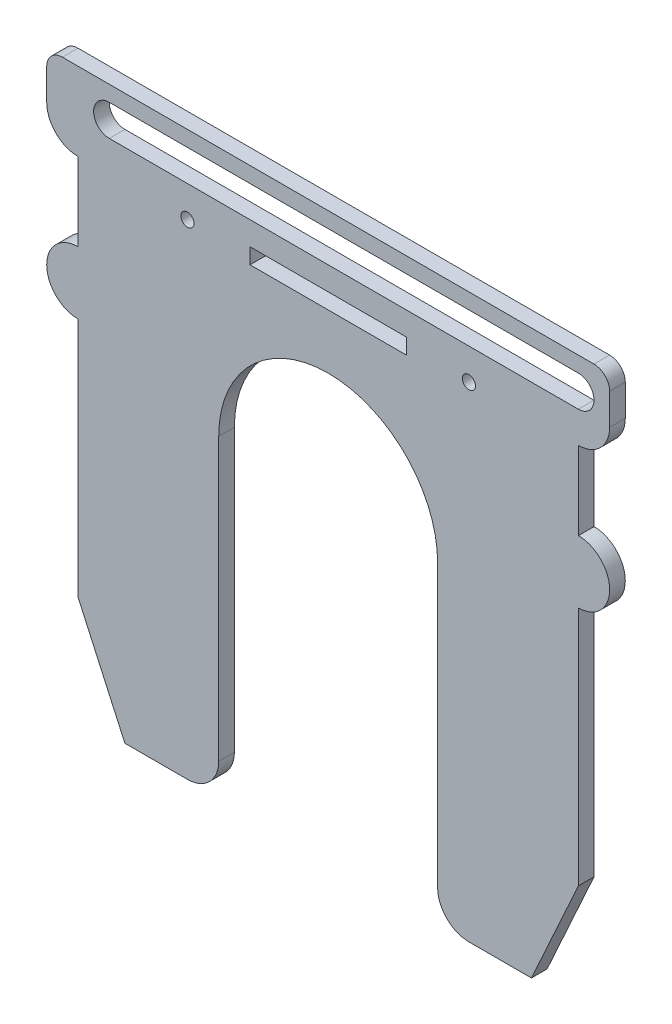
SolidWorks part; units mm, degrees
ref_plane "Front Plane" through (0, 0, 0) normal (0, 0, 1) x (1, 0, 0)
ref_plane "Top Plane" through (0, 0, 0) normal (0, 1, 0) x (1, 0, 0)
ref_plane "Right Plane" through (0, 0, 0) normal (1, 0, 0) x (0, 0, -1)
sketch "Sketch1" plane through (0, 0, 0) normal (0, 0, 1) x (1, 0, 0)
  line L0 (-160, 170) -> (-10, 170) construction
  line L1 (-10, 0) -> (-45, 0)
  line L2 (0, 10) -> (0, 175)
  line L3 (-5, 180) -> (-175, 180)
  line L4 (-180, 10) -> (-180, 175)
  line L5 (-160, 175) -> (-10, 175)
  line L6 (-160, 165) -> (-10, 165)
  line L7 (-125, 10) -> (-125, 100)
  line L8 (-55, 10) -> (-55, 100)
  line L9 (-135, 0) -> (-170, 0)
  arc A0 (-160, 175) -> (-160, 165) centre (-160, 170) ccw
  arc A1 (-10, 165) -> (-10, 175) centre (-10, 170) ccw
  arc A2 (0, 175) -> (-5, 180) centre (-5, 175) ccw
  arc A3 (-175, 180) -> (-180, 175) centre (-175, 175) ccw
  arc A4 (-10, 0) -> (0, 10) centre (-10, 10) ccw
  arc A5 (-170, 0) -> (-180, 10) centre (-170, 10) cw
  arc A8 (-125, 100) -> (-55, 100) centre (-90, 100) cw
  arc A9 (-55, 10) -> (-45, 0) centre (-45, 10) ccw
  arc A10 (-125, 10) -> (-135, 0) centre (-135, 10) cw
  point P7 (-85, 170)
  point P14 (0, 180)
  point P17 (-180, 180)
  point P20 (0, 0)
  point P23 (-180, 0)
  point P31 (-55, 0)
  point P34 (-125, 0)
  dimension "D3" = 5
  dimension "D5" = 20
  dimension "D6" = 10
  dimension "D7" = 5
  dimension "D8" = 10
  dimension "D9" = 100
  dimension "D12" = 35
  dimension "D11" = 10
  dimension "D1" = 180
  dimension "D2" = 180
  dimension "D4" = 150
  dimension "D10" = 100
extrude "Boss-Extrude1" add sketch "Sketch1" along normal blind 5
sketch "Sketch2" plane through (0, 0, 5) normal (0, 0, 1) x (1, 0, 0)
  line L0 (-180, 175) -> (-180, 10) construction
  line L1 (-115, 157.5) -> (-65, 157.5)
  line L2 (-115, 157.5) -> (-115, 152.5)
  line L3 (-115, 152.5) -> (-65, 152.5)
  line L4 (-65, 157.5) -> (-65, 152.5)
  line L5 (-160, 165) -> (-10, 165) construction
  circle A0 centre (-135, 155) radius 2.1
  circle A1 centre (-45, 155) radius 2.1
  point P4 (-90, 157.5)
  dimension "D5" = 4.2
  dimension "D6" = 4.2
  dimension "D7" = 20
  dimension "D8" = 20
  dimension "D9" = 2.5
  dimension "D10" = 2.5
  dimension "D1" = 50
  dimension "D2" = 5
  dimension "D3" = 90
  dimension "D4" = 7.5
extrude "Cut-Extrude1" cut sketch "Sketch2" against normal blind 10
sketch "Sketch3" plane through (0, 0, 5) normal (0, 0, 1) x (1, 0, 0)
  line L0 (0, 55) -> (0, 0)
  line L1 (0, 10) -> (0, 175) construction
  line L2 (0, 0) -> (-25, 0)
  line L3 (-45, 0) -> (-10, 0) construction
  line L4 (-25, 0) -> (0, 55)
  line L5 (-90, 135) -> (-90, 114.5851) construction
  line L6 (-155, 0) -> (-180, 55)
  line L7 (-180, 0) -> (-155, 0)
  line L8 (-180, 55) -> (-180, 0)
  arc A0 (-55, 100) -> (-125, 100) centre (-90, 100) ccw construction
  dimension "D1" = 55
  dimension "D2" = 25
extrude "Cut-Extrude2" cut sketch "Sketch3" against normal blind 10
sketch "Sketch4" plane through (0, 0, 5) normal (0, 0, 1) x (1, 0, 0)
  line L0 (0, 155) -> (-10, 155)
  line L1 (0, 55) -> (0, 175) construction
  line L2 (-10, 155) -> (-10, 33)
  line L3 (0, 55) -> (-25, 0) construction
  line L4 (-5, 180) -> (-175, 180) construction
  line L5 (0, 155) -> (0, 55)
  line L6 (0, 55) -> (-10, 33)
  line L7 (-90, 180) -> (-90, 169.9729) construction
  line L8 (-180, 55) -> (-170, 33)
  line L9 (-180, 155) -> (-180, 55)
  line L10 (-170, 155) -> (-170, 33)
  line L11 (-180, 155) -> (-170, 155)
  dimension "D1" = 10
  dimension "D2" = 25
extrude "Cut-Extrude3" cut sketch "Sketch4" against normal blind 10
fillet "Fillet1" radius 10 2 edges at (0, 155, 2.5) (-180, 155, 2.5)
sketch "Sketch5" plane through (0, 0, 5) normal (0, 0, 1) x (1, 0, 0)
  line L0 (-10, 155) -> (-10, 33) construction
  line L1 (-10, 130) -> (-10, 110)
  line L2 (-5, 180) -> (-175, 180) construction
  arc A0 (-10, 110) -> (-10, 130) centre (-10, 120) ccw
  dimension "D1" = 60
extrude "Boss-Extrude2" add sketch "Sketch5" against normal blind 5
ref_plane "Plane1" through (-90, 0, 0) normal (1, 0, 0) x (0, 0, -1)
mirror "Mirror1" about plane through (-90, 0, 0) normal (1, 0, 0) of "Boss-Extrude2"
